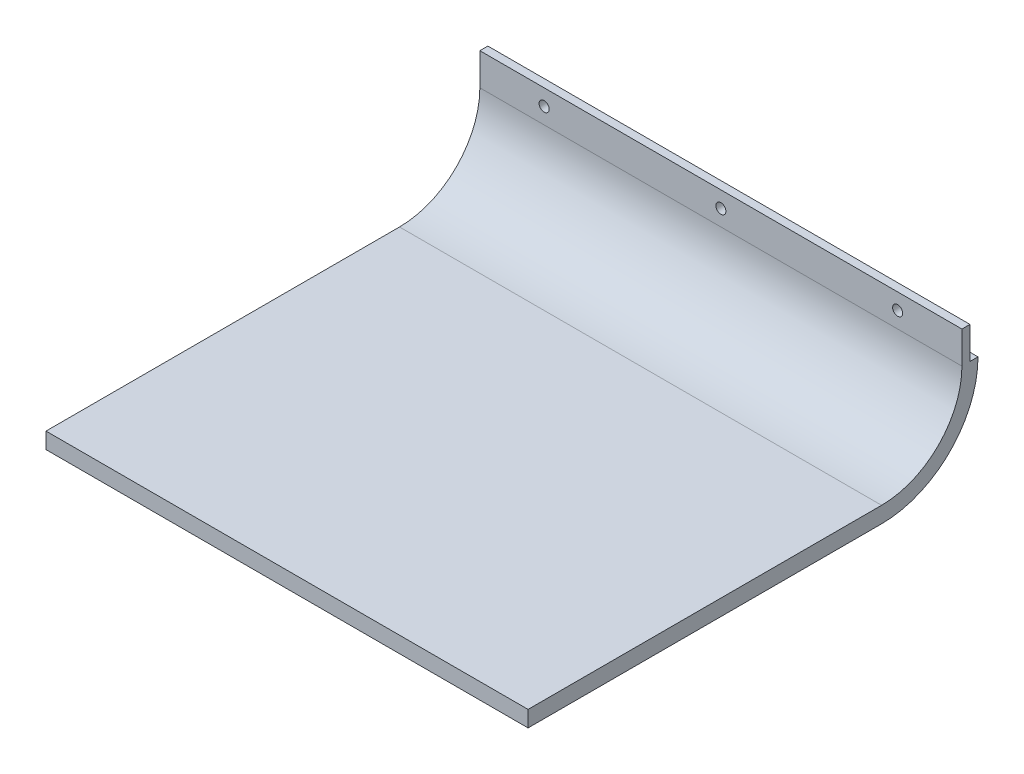
SolidWorks part; units mm, degrees
ref_plane "Front Plane" through (0, 0, 0) normal (0, 0, 1) x (1, 0, 0)
ref_plane "Top Plane" through (0, 0, 0) normal (0, 1, 0) x (1, 0, 0)
ref_plane "Right Plane" through (0, 0, 0) normal (1, 0, 0) x (0, 0, -1)
sketch "Sketch1" plane through (0, 0, 0) normal (1, 0, 0) x (0, 0, -1)
  line L0 (-139.7, 0) -> (139.7, 0)
  line L5 (139.7, 0) -> (139.7, 12.7) construction
  line L7 (-139.7, 12.7) -> (139.7, 12.7)
  line L9 (-139.7, 0) -> (-139.7, 12.7)
  line L12 (139.7, 0) -> (139.7, 152.4) construction
  line L13 (0.6365, 139.0796) -> (-139.7417, 139.9778) construction
  line L14 (-12.6991, 151.8652) -> (-139.6605, 152.6775) construction
  line L15 (203.2, 76.2) -> (215.9, 76.2)
  arc A2 (139.7, 0) -> (-12.6991, 151.8652) centre (139.7, 152.4) ccw construction
  arc A3 (139.7, 12.7) -> (0.6365, 139.0796) centre (139.7, 152.4) ccw construction
  circle A5 centre (139.7, 76.2) radius 76.2 construction
  arc A6 (215.9, 76.2) -> (139.7, 0) centre (139.7, 76.2) cw
  circle A7 centre (139.7, 76.2) radius 63.5 construction
  arc A8 (203.2, 76.2) -> (139.7, 12.7) centre (139.7, 76.2) cw
  point P3 (0, 0)
  dimension "D1" = 152.4
  dimension "D2" = 12.7
  dimension "D4" = 127
  dimension "D6" = 12.7
  dimension "D3" = 12.7
  dimension "D5" = 12.7
  dimension "D7" = 355.6
extrude "Boss-Extrude1" add sketch "Sketch1" along normal blind 190.5 and the other way blind 190.5
sketch "Sketch2" plane through (0, 76.2, 0) normal (0, 1, 0) x (1, 0, 0)
  line L0 (-190.5, 215.9) -> (-190.5, 203.2) construction
  line L1 (-190.5, 209.55) -> (190.5, 209.55)
  line L2 (-190.5, 209.55) -> (-190.5, 203.2)
  line L3 (-190.5, 203.2) -> (190.5, 203.2)
  line L4 (190.5, 209.55) -> (190.5, 203.2)
extrude "Boss-Extrude2" add sketch "Sketch2" along normal blind 25.4
sketch "Sketch3" plane through (0, 0, -209.55) normal (0, 0, -1) x (-1, 0, 0)
  line L0 (-190.5, 88.9) -> (190.5, 88.9) construction
  line L1 (-190.5, 101.6) -> (-190.5, 76.2) construction
  line L2 (190.5, 101.6) -> (190.5, 76.2) construction
  line L3 (-139.7, 101.6) -> (-139.7, 76.2) construction
  line L4 (-190.5, 101.6) -> (190.5, 101.6) construction
  line L5 (-190.5, 76.2) -> (190.5, 76.2) construction
  line L6 (0, 101.6) -> (0, 76.2) construction
  line L7 (190.5, 76.2) -> (-190.5, 76.2) construction
  line L8 (139.7, 101.6) -> (139.7, 76.2) construction
  circle A0 centre (-139.7, 88.9) radius 3.9687
  circle A1 centre (139.7, 88.9) radius 3.9687
  circle A2 centre (0, 88.9) radius 3.9687
  dimension "D3" = 7.9375
  dimension "D1" = 139.7
  dimension "D2" = 139.7
extrude "Cut-Extrude1" cut sketch "Sketch3" against normal blind 25.4
